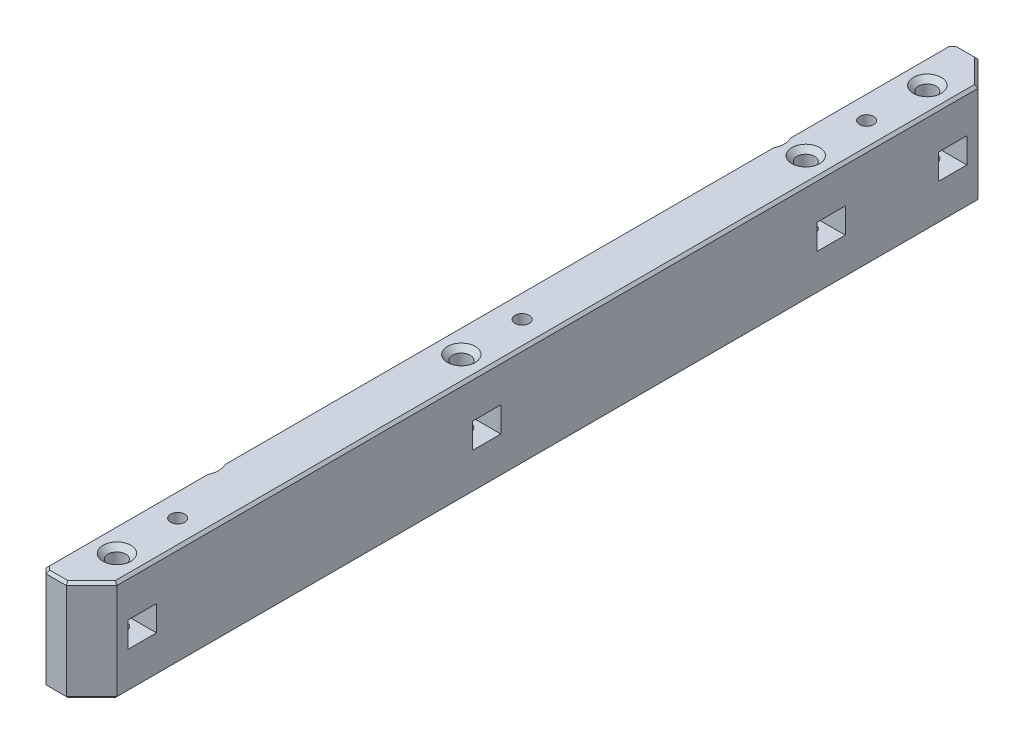
SolidWorks part; units mm, degrees
material "ABS"
ref_plane "Front Plane" through (0, 0, 0) normal (0, 0, 1) x (1, 0, 0)
ref_plane "Top Plane" through (0, 0, 0) normal (0, 1, 0) x (1, 0, 0)
ref_plane "Right Plane" through (0, 0, 0) normal (1, 0, 0) x (0, 0, -1)
sketch "Sketch1" plane through (0, 0, 0) normal (0, 0, 1) x (1, 0, 0)
  line L1 (5, -10) -> (-5, -10)
  line L2 (5, -10) -> (5, 10)
  line L3 (5, 10) -> (-5, 10)
  line L4 (-5, -10) -> (-5, 10)
  line L5 (5, -10) -> (-5, 10) construction
  line L6 (5, 10) -> (-5, -10) construction
  point P0 (0, 0)
  dimension "D1" = 10
  dimension "D2" = 20
extrude "Boss-Extrude1" add sketch "Sketch1" along normal mid plane 180
sketch "Sketch6" plane through (0, -10, 0) normal (0, -1, 0) x (1, 0, 0)
  line L0 (0, 80) -> (0, -80) construction
  circle A0 centre (0, 80) radius 1.75
  circle A1 centre (0, -80) radius 1.75
  circle A2 centre (0, 12) radius 1.75
  circle A3 centre (0, -56) radius 1.75
  dimension "D1" = 3.5
  dimension "D2" = 68
  dimension "D3" = 68
extrude "Cut-Extrude4" cut sketch "Sketch6" against normal through all
sketch "Sketch7" plane through (0, 10, 0) normal (0, 1, 0) x (1, 0, 0)
  circle A0 centre (0, 68) radius 1.4
  circle A1 centre (0, 0) radius 1.4
  circle A2 centre (0, -68) radius 1.4
  dimension "D1" = 2.8
extrude "Cut-Extrude5" cut sketch "Sketch7" against normal through all
sketch "Sketch9" plane through (0, 10, 0) normal (0, 1, 0) x (1, 0, 0)
  line L0 (5, 90) -> (-5, 90) construction
  line L1 (2.4249, -78.6) -> (1.6166, -77.2) construction
  line L2 (1.6166, -77.2) -> (-1.6166, -77.2)
  line L3 (-1.6166, -77.2) -> (-3.2332, -80)
  line L4 (-3.2332, -80) -> (-1.6166, -82.8)
  line L5 (-1.6166, -82.8) -> (1.6166, -82.8)
  line L6 (1.6166, -82.8) -> (2.4249, -81.4) construction
  line L7 (-3.2332, 80) -> (-1.6166, 77.2)
  line L8 (-1.6166, 77.2) -> (1.6166, 77.2)
  line L9 (1.6166, 77.2) -> (2.4249, 78.6) construction
  line L10 (3.2332, 80) -> (2.4249, 81.4) construction
  line L11 (1.6166, 82.8) -> (-1.6166, 82.8)
  line L12 (-1.6166, 82.8) -> (-3.2332, 80)
  line L13 (1.6166, 82.8) -> (12.7569, 82.8)
  line L15 (12.7569, 82.8) -> (12.7569, 77.2)
  line L16 (12.7569, 77.2) -> (1.6166, 77.2)
  line L17 (1.6166, -77.2) -> (12.7569, -77.2)
  line L18 (12.7569, -77.2) -> (12.7569, -82.8)
  line L19 (12.7569, -82.8) -> (1.6166, -82.8)
  line L20 (3.2332, -80) -> (2.4249, -78.6) construction
  line L21 (2.4249, -81.4) -> (3.2332, -80) construction
  line L22 (2.4249, 81.4) -> (1.6166, 82.8) construction
  line L23 (2.4249, 78.6) -> (3.2332, 80) construction
  line L24 (1.6166, -9.2) -> (-1.6166, -9.2)
  line L25 (-1.6166, -9.2) -> (-3.2332, -12)
  line L26 (-3.2332, -12) -> (-1.6166, -14.8)
  line L27 (-1.6166, -14.8) -> (1.6166, -14.8)
  line L28 (1.6166, -9.2) -> (12.7569, -9.2)
  line L29 (12.7569, -9.2) -> (12.7569, -14.8)
  line L30 (12.7569, -14.8) -> (1.6166, -14.8)
  line L31 (2.4249, -10.6) -> (1.6166, -9.2) construction
  line L32 (1.6166, -14.8) -> (2.4249, -13.4) construction
  line L33 (3.2332, -12) -> (2.4249, -10.6) construction
  line L34 (2.4249, -13.4) -> (3.2332, -12) construction
  line L35 (1.6166, 58.8) -> (-1.6166, 58.8)
  line L36 (-1.6166, 58.8) -> (-3.2332, 56)
  line L37 (-3.2332, 56) -> (-1.6166, 53.2)
  line L38 (-1.6166, 53.2) -> (1.6166, 53.2)
  line L39 (1.6166, 58.8) -> (12.7569, 58.8)
  line L40 (12.7569, 58.8) -> (12.7569, 53.2)
  line L41 (12.7569, 53.2) -> (1.6166, 53.2)
  line L42 (2.4249, 57.4) -> (1.6166, 58.8) construction
  line L43 (1.6166, 53.2) -> (2.4249, 54.6) construction
  line L44 (3.2332, 56) -> (2.4249, 57.4) construction
  line L45 (2.4249, 54.6) -> (3.2332, 56) construction
  circle A0 centre (0, -80) radius 2.8 construction
  circle A1 centre (0, 80) radius 2.8 construction
  circle A2 centre (0, -12) radius 2.8 construction
  circle A3 centre (0, 56) radius 2.8 construction
  dimension "D1" = 5.6
  dimension "D2" = 3
extrude "Cut-Extrude6" cut sketch "Sketch9" against normal mid plane 5 from offset 10 offset against normal yes
chamfer "Chamfer2" distance 5 angle 45 2 edges at (5, 0, -90) (5, 0, 90)
chamfer "Chamfer3" distance 1 angle 45 9 edges at (1.75, -10, -80) (0, -10, 1.4) (0, -10, 69.4) (1.75, 10, 80) (1.75, 10, -80) (-5, 0, -90) (-5, 0, 90) (1.75, 10, -56) (1.75, 10, 12)
chamfer "Chamfer4" distance 0.5 angle 45 8 edges at (-4.5, -10, 89.5) (-2, -10, 90) (2.5, -10, 87.5) (5, -10, 0) (2.5, -10, -87.5) (-2, -10, -90) (-4.5, -10, -89.5) (-5, -10, 0)
chamfer "Chamfer5" distance 0.5 angle 45 8 edges at (2.5, 10, -87.5) (5, 10, 0) (2.5, 10, 87.5) (-2, 10, 90) (-4.5, 10, 89.5) (-5, 10, 0) (-4.5, 10, -89.5) (-2, 10, -90)
sketch "Sketch10" plane through (0, -10, 0) normal (0, -1, 0) x (1, 0, 0)
  circle A0 centre (-7.8485, -55.8836) radius 3.75
  circle A1 centre (-7.8485, 55.8836) radius 3.75
  dimension "D1" = 7.5
extrude "Cut-Extrude7" cut sketch "Sketch10" against normal through all
ref_plane "Plane1" through (-10, 0, 0) normal (1, 0, 0) x (0, 0, -1)
